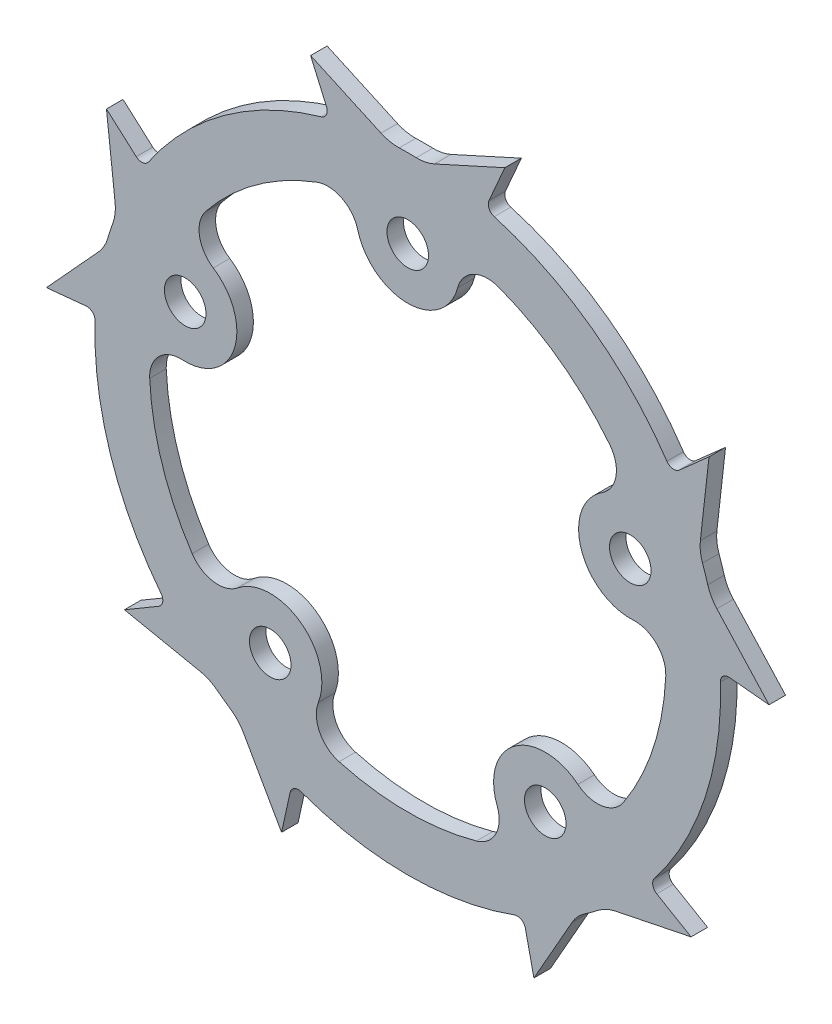
SolidWorks part; units mm, degrees
material "Alloy Steel (SS)"
ref_plane "Front Plane" through (0, 0, 0) normal (0, 0, 1) x (1, 0, 0)
ref_plane "Top Plane" through (0, 0, 0) normal (0, 1, 0) x (1, 0, 0)
ref_plane "Right Plane" through (0, 0, 0) normal (1, 0, 0) x (0, 0, -1)
sketch "Sketch1" plane through (0, 0, 0) normal (0, 0, 1) x (1, 0, 0)
  line L0 (0, 0) -> (0, 28.7588) construction
  line L1 (0, 0) -> (27.3512, 8.8869) construction
  line L2 (0, 0) -> (16.904, -23.2663) construction
  line L3 (0, 0) -> (-16.904, -23.2663) construction
  line L4 (0, 0) -> (-27.3512, 8.8869) construction
  line L5 (-9.5106, 37.2552) -> (-11.938, 42.8169)
  line L6 (-11.938, 42.8169) -> (0, 0) construction
  line L7 (-11.938, 42.8169) -> (-3.2859, 38.8883)
  line L8 (0, 0) -> (0, 44.45) construction
  line L9 (9.5106, 37.2552) -> (11.938, 42.8169)
  line L10 (11.938, 42.8169) -> (3.2859, 38.8883)
  line L11 (-10.3266, 37.0373) -> (13.7805, 43.7588) construction
  line L12 (-11.938, 42.8169) -> (-5.2343, 44.686) construction
  circle A0 centre (0, 0) radius 44.45 construction
  circle A1 centre (0, 0) radius 31.75
  circle A2 centre (0, 28.7588) radius 2.5527
  arc A3 (6.1383, 27.1326) -> (-6.1383, 27.1326) centre (0, 28.7588) cw
  arc A4 (6.1383, 27.1326) -> (11.1605, 29.7238) centre (9.8212, 26.157) cw
  arc A5 (-6.1383, 27.1326) -> (-11.1605, 29.7238) centre (-9.8212, 26.157) ccw
  arc A6 (23.9079, 14.2223) -> (24.8203, 19.7994) centre (21.8418, 17.4235) ccw
  arc A7 (27.7015, 2.5466) -> (23.9079, 14.2223) centre (27.3512, 8.8869) cw
  circle A8 centre (27.3512, 8.8869) radius 2.5527
  arc A9 (27.7015, 2.5466) -> (31.7178, -1.4291) centre (27.9117, -1.2576) cw
  arc A10 (20.9141, -18.3428) -> (26.5002, -17.4871) centre (23.3202, -15.3887) ccw
  arc A11 (10.9822, -25.5588) -> (20.9141, -18.3428) centre (16.904, -23.2663) cw
  circle A12 centre (16.904, -23.2663) radius 2.5527
  arc A13 (10.9822, -25.5588) -> (8.4422, -30.607) centre (7.4292, -26.9342) cw
  arc A14 (-10.9822, -25.5588) -> (-8.4422, -30.607) centre (-7.4292, -26.9342) ccw
  arc A15 (-20.9141, -18.3428) -> (-10.9822, -25.5588) centre (-16.904, -23.2663) cw
  circle A16 centre (-16.904, -23.2663) radius 2.5527
  arc A17 (-20.9141, -18.3428) -> (-26.5002, -17.4871) centre (-23.3202, -15.3887) cw
  arc A18 (-27.7015, 2.5466) -> (-31.7178, -1.4291) centre (-27.9117, -1.2576) ccw
  arc A19 (-23.9079, 14.2223) -> (-27.7015, 2.5466) centre (-27.3512, 8.8869) cw
  circle A20 centre (-27.3512, 8.8869) radius 2.5527
  arc A21 (-23.9079, 14.2223) -> (-24.8203, 19.7994) centre (-21.8418, 17.4235) cw
  circle A22 centre (0, 0) radius 38.45
  arc A23 (-3.2859, 38.8883) -> (-1.0473, 38.4357) centre (-1.1856, 43.5139) ccw
  arc A24 (3.2859, 38.8883) -> (1.0473, 38.4357) centre (1.1856, 43.5139) cw
  point P47 (0, 0)
  point P57 (0, 28.7588)
  dimension "D1" = 88.9
  dimension "D2" = 63.5
  dimension "D3" = 5.1054
  dimension "D4" = 28.7588
  dimension "D6" = 6.35
  dimension "D8" = 6
  dimension "D12" = 5.08
  dimension "D10" = 40
  dimension "D7" = 3.81
  dimension "D9" = 8
  dimension "D11" = 23.876
  dimension "D5" = 5
extrude "Boss-Extrude1" add sketch "Sketch1" along normal blind 2.032 contours A0 A1 | A19 A21 A1 A18 A20 | A5 A3 A4 A1 A2 | A7 A9 A1 A6 A8 | A11 A13 A1 A10 A12 | A15 A17 A1 A14 A16 region at (-5.1616, 37.0042, 0) region at (31.7182, -0.7142, 0) region at (7.9633, 29.7579, 0) region at (18.529, -25.503, 0) region at (-25.8367, 16.7699, 0) region at (-18.529, -25.503, 0)
extrude "Boss-Extrude5" add sketch "Sketch1<5>" along normal up to surface (2.032 mm away) contours L7 L5 A22 | A22 L9 L10 region at (-7.9331, 39.5489, 0) region at (7.9331, 39.5489, 0) up to face at (0, 0, 2.032)
sketch "Sketch1<5>" plane through (0, 0, 0) normal (0, 0, 1) x (1, 0, 0) same geometry as "Sketch1"
fillet "Fillet2" radius 1.016 2 edges at (9.5106, 37.2552, 1.016) (-9.5106, 37.2552, 1.016)
pattern_circular "CirPattern2" count 5 over 360 about axis through (0, 0, 2.032) along (0, 0, 1) of "Boss-Extrude5", "Fillet2"
